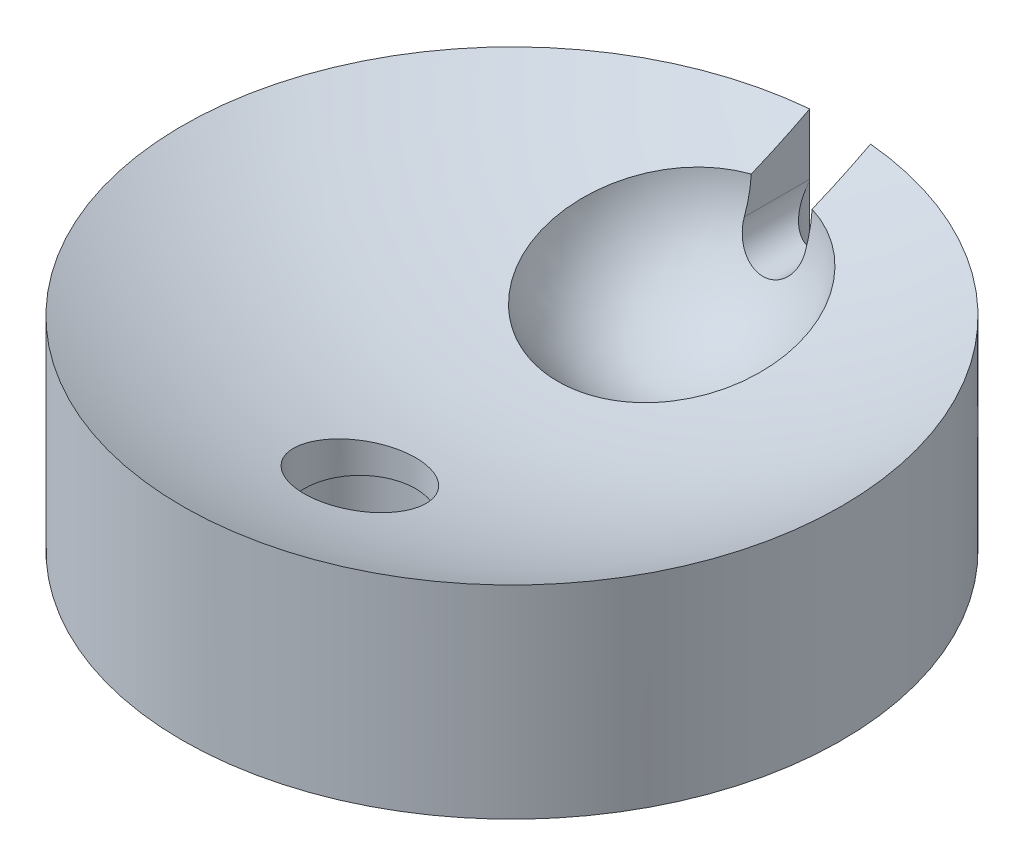
SolidWorks part; units mm, degrees
ref_plane "Front Plane" through (0, 0, 0) normal (0, 0, 1) x (1, 0, 0)
ref_plane "Top Plane" through (0, 0, 0) normal (0, 1, 0) x (1, 0, 0)
ref_plane "Right Plane" through (0, 0, 0) normal (1, 0, 0) x (0, 0, -1)
sketch "Sketch1" plane through (0, 0, 0) normal (0, 0, 1) x (1, 0, 0)
  line L0 (0, 0) -> (0, 12)
  line L1 (0, 0) -> (32.5, 0)
  line L2 (32.5, 0) -> (32.5, 20)
  line L3 (0, 12) -> (-3, 12) construction
  arc A1 (0, 12) -> (32.5, 20) centre (0, 82.0156) ccw
  point P3 (0.1801, 5)
  point P6 (32.5, 16.5453)
  point P8 (32.5, 18.1778)
  dimension "D4" = 20
  dimension "D1" = 12
  dimension "D2" = 32.5
  dimension "D3" = 3
revolve "BASE" add sketch "Sketch1" angle 360 about L0
sketch "Sketch2" plane through (0, 0, 0) normal (0, -1, 0) x (1, 0, 0)
  arc A3 (-2.9968, -32.3615) -> (2.9968, -32.3615) centre (0, -32.5) cw
  circle A4 centre (0, 0) radius 32.5 construction
  arc A5 (-2.9968, -32.3615) -> (2.9968, -32.3615) centre (0, 0) ccw
  point P3 (0.5484, -31.1032)
  point P7 (0, 0)
  point P8 (0, 0)
  dimension "D1" = 3
extrude "WIRE PASSTHRU" cut sketch "Sketch2" against normal through all
sketch "Sketch3" plane through (0, 0, 0) normal (1, 0, 0) x (0, 0, -1)
  line L0 (15, 18) -> (15, 6)
  line L1 (15, 18) -> (27, 18)
  arc A0 (15, 6) -> (27, 18) centre (15, 18) ccw
  dimension "D1" = 12
  dimension "D2" = 15
  dimension "D3" = 6
revolve "DEPLOYMENT CHARGE CAVITY" cut sketch "Sketch3" angle 360 about L0
ref_plane "Plane1" through (0, 0, -8) normal (0, 0, -1) x (-1, 0, 0)
sketch "Sketch5" plane through (0, 0, -8) normal (0, 0, 1) x (1, 0, 0)
  line L0 (-3, 14) -> (-3, 20)
  line L1 (32.5, 20) -> (-32.5, 20) construction
  line L2 (-3, 20) -> (3, 20)
  line L3 (3, 20) -> (3, 14)
  arc A0 (-3, 14) -> (3, 14) centre (0, 14) ccw
  point P7 (0, 0)
  dimension "D1" = 3
  dimension "D2" = 6
extrude "WIRE PASSTHRU PT2" cut sketch "Sketch5" against normal through all
sketch "Sketch6" plane through (0, 0, 0) normal (0, -1, 0) x (1, 0, 0)
  circle A0 centre (0, 15) radius 5.5
  point P2 (0, 0)
  dimension "D1" = 11
  dimension "D2" = 15
extrude "CAMERA LENS CUT PT1" cut sketch "Sketch6" against normal through all
sketch "Sketch8" plane through (0, 0, 0) normal (0, -1, 0) x (1, 0, 0)
  circle A0 centre (0, 15) radius 6
  circle A1 centre (0, 15) radius 5.5 construction
  dimension "D1" = 12
extrude "CAMERA LENS CUT PT2" cut sketch "Sketch8" against normal blind 10
sketch "Sketch9" plane through (0, 0, 0) normal (0, -1, 0) x (1, 0, 0)
  line L1 (-7.5, 22.5) -> (7.5, 22.5)
  line L2 (-7.5, 22.5) -> (-7.5, 7.5)
  line L3 (-7.5, 7.5) -> (7.5, 7.5)
  line L4 (7.5, 22.5) -> (7.5, 7.5)
  line L5 (-7.5, 22.5) -> (7.5, 7.5) construction
  line L6 (-7.5, 7.5) -> (7.5, 22.5) construction
  point P0 (0, 15)
  dimension "D1" = 15
extrude "CAMERA PCB CUT" cut sketch "Sketch9" against normal blind 2
sketch "Sketch10" plane through (0, 0, 0) normal (0, -1, 0) x (1, 0, 0)
  line L1 (-10.5, -17) -> (10.5, -17)
  line L2 (-10.5, -17) -> (-10.5, -23)
  line L3 (-10.5, -23) -> (10.5, -23)
  line L4 (10.5, -17) -> (10.5, -23)
  point P4 (0, -17)
  dimension "D1" = 17
  dimension "D2" = 6
  dimension "D3" = 21
extrude "ALIGNMENT PEG CUTOUT" cut sketch "Sketch10" against normal blind 6
fillet "Fillet1" radius 1.5 4 edges at (10.5, 0, -20) (0, 0, -23) (-10.5, 0, -20) (0, 0, -17)
